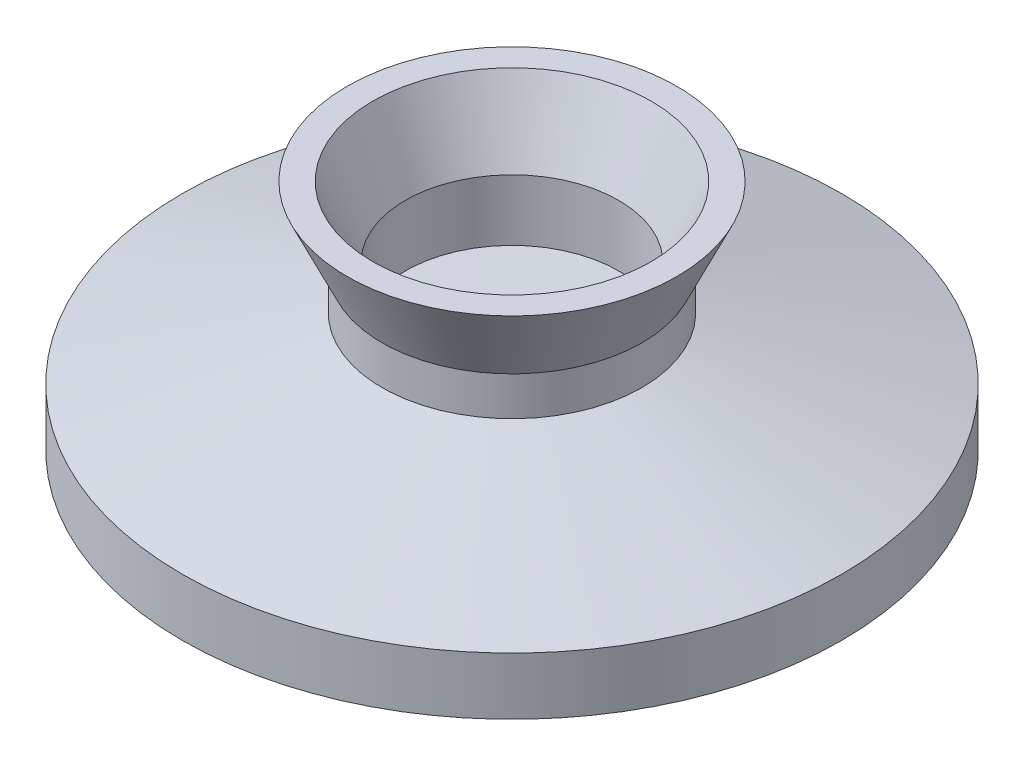
SolidWorks part; units mm, degrees
ref_plane "Front Plane" through (0, 0, 0) normal (0, 0, 1) x (1, 0, 0)
ref_plane "Top Plane" through (0, 0, 0) normal (0, 1, 0) x (1, 0, 0)
ref_plane "Right Plane" through (0, 0, 0) normal (1, 0, 0) x (0, 0, -1)
sketch "Sketch1" plane through (0, 0, 0) normal (0, 0, 1) x (1, 0, 0)
  line L0 (78.4718, -15.7491) -> (4.2164, -20.2908)
  line L1 (0, -201655.0005) -> (0, 281095.0265) construction
  line L3 (4.2164, -20.2908) -> (4.2164, -26.2734)
  line L5 (85, -11.4863) -> (33.5, 4.426)
  line L6 (33.5, 4.426) -> (33.5, 14.426)
  line L8 (78.4718, -15.7491) -> (27.5, 0)
  line L9 (27.5, 0) -> (27.5, 15.7562)
  line L15 (0, -1021.2131) -> (0, 48978.7869) construction
  line L19 (33.5, 14.426) -> (42.5, 33.7266)
  line L20 (42.5, 33.7266) -> (35.8797, 33.7266)
  line L22 (27.5, 0) -> (27.5, 94) construction
  line L23 (33.5, 4.426) -> (33.5, 94) construction
  line L24 (35.8797, 33.7266) -> (27.5, 15.7562)
  line L25 (80.243, -10.0165) -> (33.5, 4.426) construction
  line L26 (4.2164, -26.2734) -> (85, -26.2734)
  line L27 (85, -26.2734) -> (85, -11.4863)
  point P8 (0, 0)
  point P9 (0, 0)
  point P10 (0, 0)
  point P11 (0, 0)
  point P12 (67.5362, -23.4976)
  point P20 (0, 0)
  point P21 (0, 0)
  point P22 (52.0559, -20.6506)
  point P24 (77.3226, -19.3412)
  point P26 (67.7141, -20.1252)
  point P27 (87.2547, -20.4197)
  point P28 (77.2487, -22.4021)
  point P30 (78.6081, -23.3404)
  point P32 (79.4338, -20.1752)
  point P33 (78.2927, -20.5026)
  point P34 (0, 0)
  point P35 (0, 0)
  point P36 (0, 0)
  point P37 (0, 0)
  point P39 (0, 0)
  dimension "D9" = 25
  dimension "D12" = 6
  dimension "D14" = 60
  dimension "D13" = 27.5
  dimension "D15" = 10
  dimension "D2" = 85
  dimension "D8" = 42.5
  dimension "D10" = 3.5
  dimension "D4" = 6.5282
  dimension "D5" = 14.7871
  dimension "8.4328/2" = 4.2164
  dimension "D3" = 6
revolve "Revolve2" add sketch "Sketch1" angle 360 about L15
sketch "Sketch2" plane through (0, 0, 0) normal (0, 0, 1) x (1, 0, 0)
  line L1 (0, -27.3205) -> (81.4732, -22.6761)
  line L2 (81.4732, -22.6761) -> (81.4732, -18.432)
  line L6 (0, -14.7943) -> (71.5769, -14.7943)
  line L8 (71.5769, -14.7943) -> (81.4732, -18.432)
  line L9 (0, -201021.2131) -> (0, 248978.7869) construction
  line L10 (0, -14.7943) -> (0, -27.3205)
  point P2 (0, -25.7782)
  point P4 (0, -28.4966)
  point P6 (59.79, -8.0676)
  point P7 (61.8745, -8.8723)
  point P10 (68.1642, -13.2586)
  point P11 (71.109, -14.6926)
  point P12 (72.6459, -15.458)
  point P13 (0, -29.8143)
  point P14 (0, 0)
  point P15 (0, 0)
  point P16 (0, -32.6386)
  point P17 (0, 0)
  point P18 (62.666, -12.5053)
  point P19 (0, 0)
  point P20 (0, -27.3205)
  point P21 (69.6257, -15.3014)
  point P22 (69.004, -13.9382)
  point P23 (70.1219, -14.443)
  point P24 (71.969, -15.2889)
  point P25 (71.5769, -14.7943)
revolve "Revolve4" [suppressed] add sketch "Sketch2" angle 360 about L15
other "Intersect1" [suppressed]
equation "\"D12@Sketch1\"=\"D3@Sketch1\""
